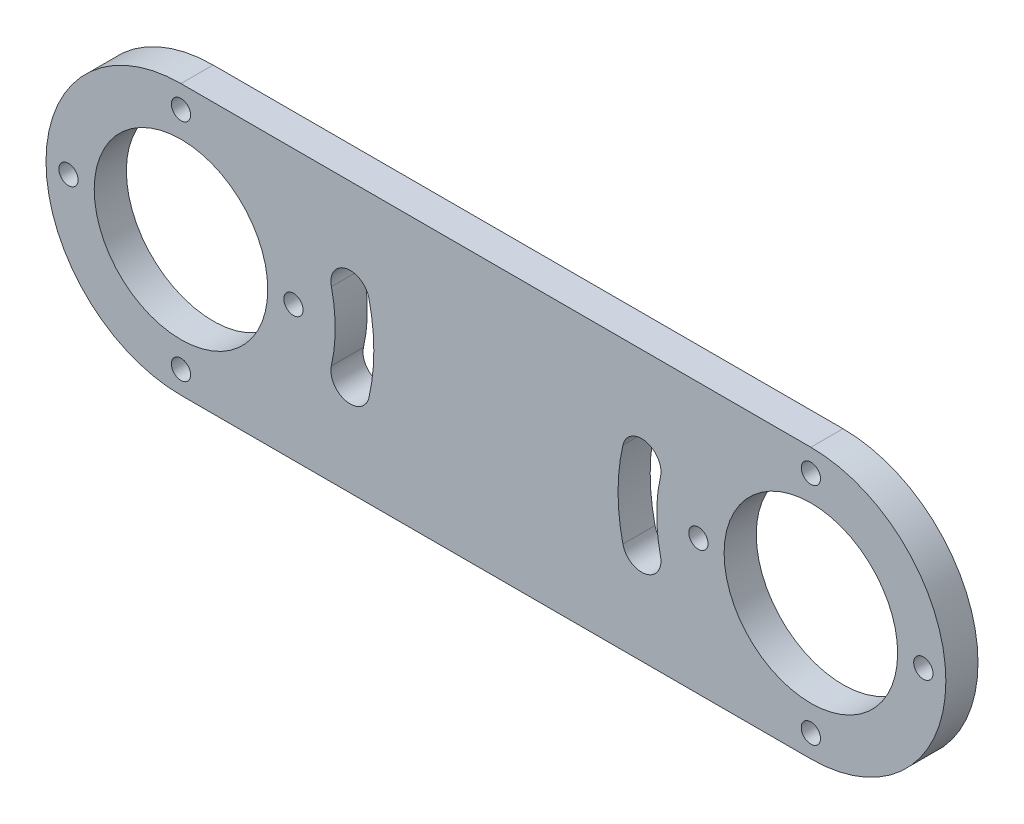
SolidWorks part; units mm, degrees
material "Thornel Mat VMA"
ref_plane "Front Plane" through (0, 0, 0) normal (0, 0, 1) x (1, 0, 0)
ref_plane "Top Plane" through (0, 0, 0) normal (0, 1, 0) x (1, 0, 0)
ref_plane "Right Plane" through (0, 0, 0) normal (1, 0, 0) x (0, 0, -1)
sketch "Sketch1" plane through (0, 0, 0) normal (0, 0, 1) x (1, 0, 0)
  line L0 (-49, 26) -> (49, 26)
  line L1 (-49, -16) -> (49, -16)
  arc A1 (-49, 26) -> (-49, -16) centre (-49, 5) ccw
  arc A3 (49, -16) -> (49, 26) centre (49, 5) ccw
  arc A4 (49, -14) -> (49, -11) centre (49, -12.5) ccw construction
  arc A5 (66.5, 3.5) -> (66.5, 6.5) centre (66.5, 5) ccw construction
  arc A6 (31.5, 3.5) -> (31.5, 6.5) centre (31.5, 5) ccw construction
  arc A7 (49, 21) -> (49, 24) centre (49, 22.5) ccw construction
  arc A8 (-49, -14) -> (-49, -11) centre (-49, -12.5) ccw construction
  arc A9 (-31.5, 3.5) -> (-31.5, 6.5) centre (-31.5, 5) ccw construction
  arc A10 (-66.5, 3.5) -> (-66.5, 6.5) centre (-66.5, 5) ccw construction
  arc A11 (-49, 24) -> (-49, 21) centre (-49, 22.5) ccw construction
  circle A12 centre (49, -12.5) radius 1.5
  circle A13 centre (66.5, 5) radius 1.5
  circle A14 centre (31.5, 5) radius 1.5
  circle A15 centre (49, 22.5) radius 1.5
  circle A16 centre (-49, -12.5) radius 1.5
  circle A17 centre (-31.5, 5) radius 1.5
  circle A18 centre (-66.5, 5) radius 1.5
  circle A19 centre (-49, 22.5) radius 1.5
  arc A20 (-49, -8) -> (-49, 18) centre (-49, 5) ccw construction
  circle A21 centre (-49, 5) radius 13
  arc A22 (49, -8) -> (49, 18) centre (49, 5) ccw construction
  circle A23 centre (49, 5) radius 13
  dimension "D1" = 21
  dimension "D2" = 26
extrude "Boss-Extrude1" add sketch "Sketch1" along normal blind 5
sketch "Sketch2" plane through (0, 0, 0) normal (0, 0, -1) x (-1, 0, 0)
  circle A0 centre (-49, 5) radius 13.5
  circle A1 centre (49, 5) radius 13.5
  circle A2 centre (-49, 5) radius 13 construction
  dimension "D1" = 27
extrude "Cut-Extrude1" cut sketch "Sketch2" against normal blind 10
sketch "Sketch3" plane through (0, 0, 5) normal (0, 0, 1) x (1, 0, 0)
  line L0 (49, 26) -> (-49, 26) construction
  line L1 (0, 26) -> (0, -16) construction
  line L2 (-49, -16) -> (49, -16) construction
  line L3 (0, 5) -> (-11.8321, 5) construction
  circle A0 centre (49, 5) radius 24
  circle A1 centre (49, 5) radius 30
  arc A2 (19.7501, 11.6667) -> (25.6001, 10.3333) centre (22.6751, 11) cw
  arc A3 (19.7501, -1.6667) -> (25.6001, -0.3333) centre (22.6751, -1) ccw
  arc A4 (-19.7501, -1.6667) -> (-25.6001, -0.3333) centre (-22.6751, -1) cw
  arc A5 (-19.7501, 11.6667) -> (-25.6001, 10.3333) centre (-22.6751, 11) ccw
  circle A6 centre (-49, 5) radius 30
  circle A7 centre (-49, 5) radius 24
  dimension "D1" = 48
  dimension "D2" = 60
  dimension "D3" = 15
extrude "Cut-Extrude2" cut sketch "Sketch3" against normal blind 10 contours A5 A7 A4 A6 | A1 A3 A0 A2 region at (22.3515, 5, 5) region at (-22.3515, 5, 5)
